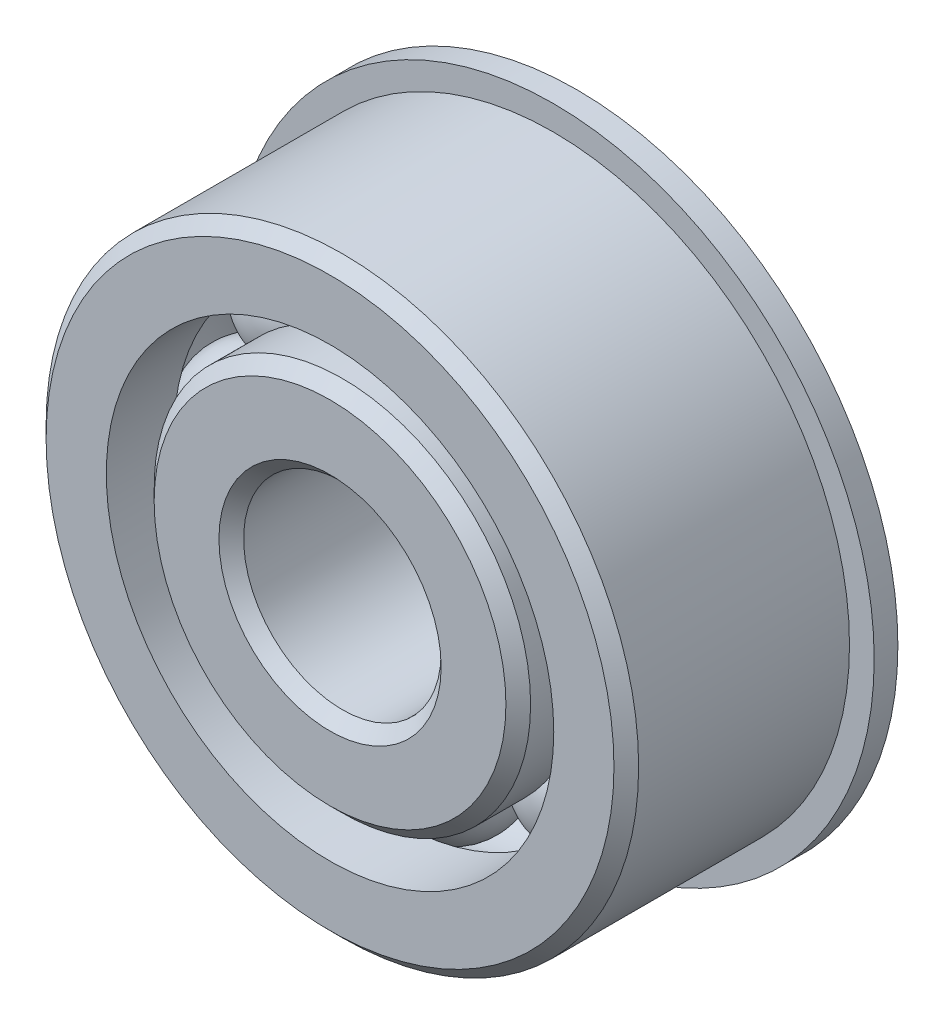
SolidWorks part; units mm, degrees
ref_plane "Front Plane" through (0, 0, 0) normal (0, 0, 1) x (1, 0, 0)
ref_plane "Top Plane" through (0, 0, 0) normal (0, 1, 0) x (1, 0, 0)
ref_plane "Right Plane" through (0, 0, 0) normal (1, 0, 0) x (0, 0, -1)
sketch "Sketch1" plane through (0, 0, 0) normal (1, 0, 0) x (0, 0, -1)
  line L0 (-7.9375, 0) -> (7.9375, 0) construction
  line L1 (0, 19.05) -> (0, -19.05) construction
  line L2 (7.1438, 19.05) -> (-7.1437, 19.05)
  line L3 (-7.1437, 19.05) -> (-7.9375, 18.2563)
  line L4 (-7.9375, 18.2563) -> (-7.9375, 14.3859)
  line L5 (-7.9375, 14.3859) -> (-3.5929, 14.3859)
  line L6 (7.9375, 14.3859) -> (3.5929, 14.3859)
  line L7 (7.9375, 18.2563) -> (7.9375, 14.3859)
  line L8 (7.1438, 19.05) -> (7.9375, 18.2563)
  line L9 (0, 19.05) -> (0, 12.7) construction
  line L10 (0, 12.7) -> (0, 6.35) construction
  line L11 (7.9375, 12.1031) -> (7.9375, -12.1031) construction
  line L12 (-7.9375, 6.35) -> (7.9375, 6.35) construction
  line L13 (0, 8.7312) -> (0, 6.35) construction
  line L14 (0, 16.6687) -> (0, 19.05) construction
  line L15 (7.9375, 12.1031) -> (0, 12.1031) construction
  circle A1 centre (0, 12.7) radius 3.9688 construction
  arc A2 (-3.5929, 14.3859) -> (3.5929, 14.3859) centre (0, 12.7) cw
  point P14 (0, 6.35)
  point P22 (0, 8.7312)
  point P23 (0, 16.6687)
  dimension "D3" = 7.9375
  dimension "Width" = 15.875
  dimension "OD" = 38.1
  dimension "D1" = 45
  dimension "D2" = 0.7937
  dimension "D4" = 24.2062
  dimension "D5" = 4.5657
  dimension "D6" = 2.2828
revolve "Revolve1" add sketch "Sketch1" angle 360 about L0
sketch "Sketch3" plane through (0, 0, 0) normal (1, 0, 0) x (0, 0, -1)
  line L1 (-7.9375, 18.2563) -> (-7.9375, 14.3859) construction
  line L2 (-7.1437, 19.05) -> (-7.9375, 18.2563) construction
  line L3 (-7.9375, 11.0141) -> (-7.9375, 7.1437) construction
  line L4 (-7.9375, 7.1437) -> (-7.9375, 11.3094)
  line L5 (-7.9375, 7.1437) -> (-7.1438, 6.35)
  line L6 (-7.1438, 6.35) -> (8.7439, 6.35)
  line L7 (-7.9375, 18.2563) -> (-7.9375, -18.2563) construction
  line L8 (8.7439, 6.35) -> (9.5377, 7.1437)
  line L9 (0, 0) -> (9.5377, 0) construction
  line L13 (7.1438, 19.05) -> (7.9375, 18.2563) construction
  line L14 (-7.9375, 11.3094) -> (-7.1438, 12.1031)
  line L15 (-7.1438, 12.1031) -> (-3.9236, 12.1031)
  line L16 (3.9236, 12.1031) -> (8.7439, 12.1031)
  line L17 (8.7439, 12.1031) -> (9.5377, 11.3094)
  line L18 (9.5377, 11.3094) -> (9.5377, 7.1437)
  circle A0 centre (0, 12.7) radius 3.9688 construction
  arc A1 (-3.9236, 12.1031) -> (3.9236, 12.1031) centre (0, 12.7) ccw
  dimension "D1" = 45
  dimension "Ring Wd" = 17.4752
  dimension "Inner Ring OD" = 24.2062
revolve "Revolve3" add sketch "Sketch3" angle 360 about L0
sketch "Sketch6" plane through (0, 0, 0) normal (1, 0, 0) x (0, 0, -1)
  line L1 (7.9375, 14.3859) -> (6.4135, 14.3859)
  line L2 (7.9375, 14.3859) -> (7.9375, 20.6375)
  line L3 (7.9375, 20.6375) -> (6.4135, 20.6375)
  line L4 (6.4135, 14.3859) -> (6.4135, 20.6375)
  line L5 (7.9375, 0) -> (-7.9375, 0) construction
  dimension "Flange OD" = 41.275
  dimension "Flange Thickness" = 1.524
revolve "Revolve6" add sketch "Sketch6" angle 360 about L5
sketch "Sketch4" plane through (0, 0, 0) normal (1, 0, 0) x (0, 0, -1)
  line L0 (-3.9688, 12.7) -> (3.9688, 12.7)
  circle A0 centre (0, 12.7) radius 3.9688 construction
  arc A1 (3.9688, 12.7) -> (-3.9688, 12.7) centre (0, 12.7) ccw
revolve "Revolve4" add sketch "Sketch4" angle 360 about L0
ref_axis "Axis1" through (0, 0, -7.9375) along (0, 0, 1)
pattern_circular "CirPattern1" count 8 every 45 about axis through (0, 0, -7.9375) along (0, 0, 1) of bodies 104
sketch "Sketch5" plane through (0, 0, 0) normal (1, 0, 0) x (0, 0, -1)
  line L0 (-7.9375, 14.3859) -> (-3.5929, 14.3859) construction
  line L1 (-7.5406, 14.3859) -> (-3.9236, 14.3859)
  line L2 (-7.5406, 14.3859) -> (-7.5406, 12.1031)
  line L3 (-7.5406, 12.1031) -> (-3.9236, 12.1031)
  line L4 (-3.9236, 14.3859) -> (-3.9236, 12.1031)
  line L6 (7.9375, 14.3859) -> (3.5929, 14.3859) construction
  line L7 (7.5406, 14.3859) -> (3.9236, 14.3859)
  line L8 (7.5406, 14.3859) -> (7.5406, 12.1031)
  line L9 (7.5406, 12.1031) -> (3.9236, 12.1031)
  line L10 (3.9236, 14.3859) -> (3.9236, 12.1031)
  line L12 (-7.1437, 19.05) -> (-7.9375, 18.2563) construction
  line L13 (7.9375, 12.1031) -> (0, 12.1031) construction
  line L15 (-7.1438, 12.1031) -> (-3.9236, 12.1031) construction
  line L16 (7.5406, 14.3859) -> (7.5406, 18.6531) construction
  line L17 (7.1438, 19.05) -> (7.9375, 18.2563) construction
  point P18 (-7.5406, 18.6531)
revolve "Revolve5" [suppressed] add sketch "Sketch5" angle 360 about L0
equation "\"D2@Sketch1\" = \"Width@Sketch1\"*.05"
equation "\"D2@CirPattern1\" = 360/\"Balls@CirPattern1\""
equation "\"D4@Sketch1\"=\"Inner Ring OD@Sketch3\""
equation "\"D3@Sketch1\"=\"Width@Sketch1\"/2."
equation "\"D6@Sketch1\"=\"D5@Sketch1\"/2"
